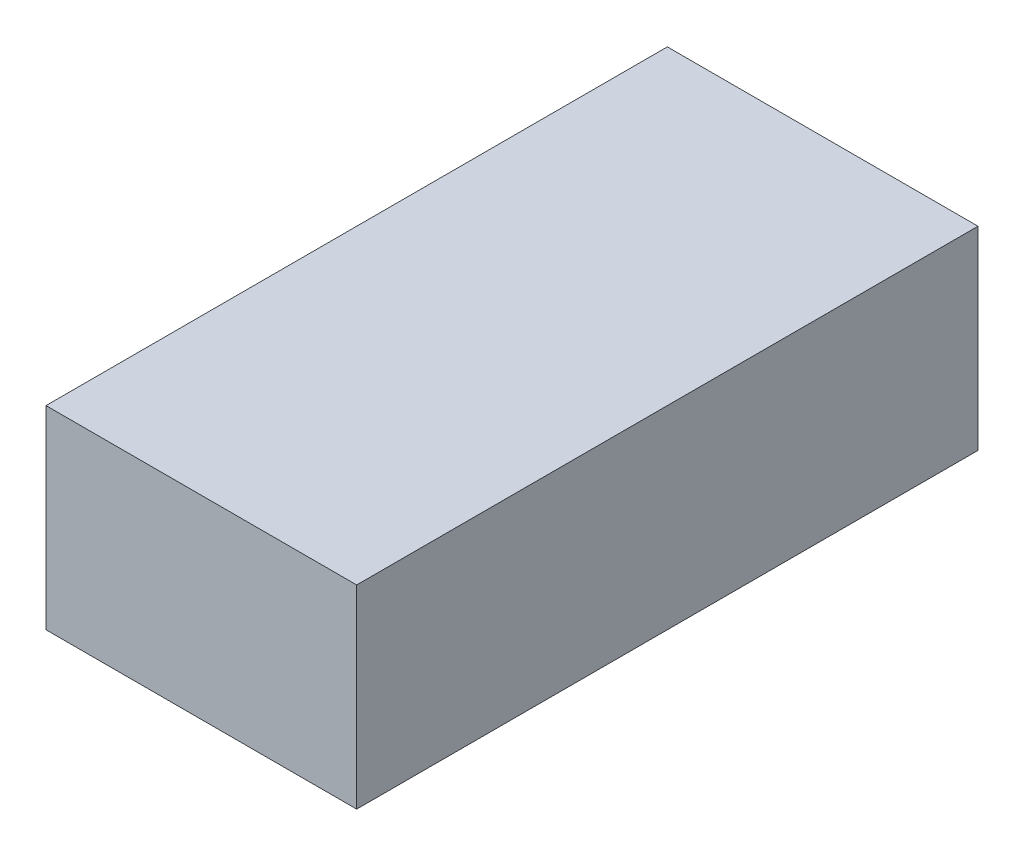
SolidWorks part; units mm, degrees
ref_plane "Front Plane" through (0, 0, 0) normal (0, 0, 1) x (1, 0, 0)
ref_plane "Top Plane" through (0, 0, 0) normal (0, 1, 0) x (1, 0, 0)
ref_plane "Right Plane" through (0, 0, 0) normal (1, 0, 0) x (0, 0, -1)
sketch "Sketch1" plane through (0, 0, 0) normal (0, 0, 1) x (1, 0, 0)
  line L7 (0, 0) -> (-80, 0)
  line L8 (0, 0) -> (0, 50)
  line L9 (0, 50) -> (-80, 50)
  line L10 (-80, 0) -> (-80, 50)
  dimension "D1" = 80
  dimension "D2" = 50
extrude "Boss-Extrude1" add sketch "Sketch1" along normal blind 160
equation "\"height\"=50"
equation "\"width\"=80"
equation "\"D1@Sketch1\"=\"width\""
equation "\"D2@Sketch1\"=\"height\""
equation "\"length\"=160"
equation "\"D1@Boss-Extrude1\"=\"length\""
